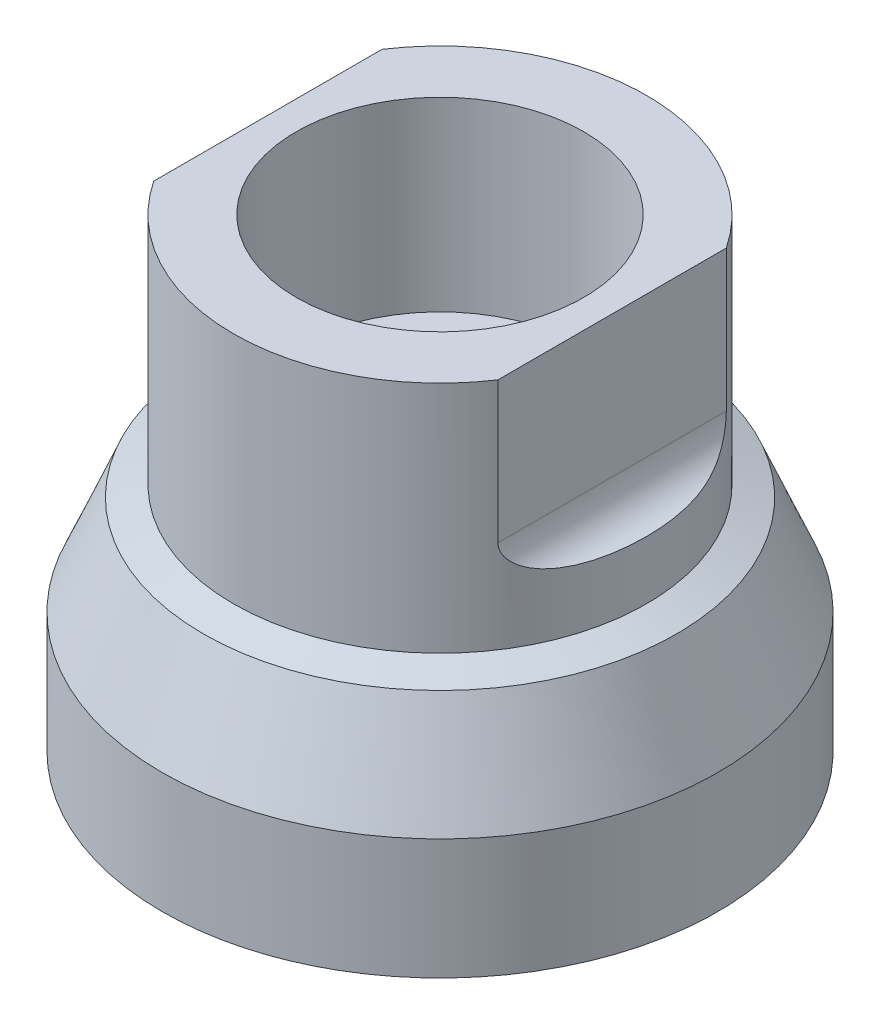
SolidWorks part; units mm, degrees
ref_plane "Front Plane" through (0, 0, 0) normal (0, 0, 1) x (1, 0, 0)
ref_plane "Top Plane" through (0, 0, 0) normal (0, 1, 0) x (1, 0, 0)
ref_plane "Right Plane" through (0, 0, 0) normal (1, 0, 0) x (0, 0, -1)
sketch "Sketch1" plane through (0, 0, 0) normal (1, 0, 0) x (0, 0, -1)
  line L0 (0, 0) -> (0, 17.2593) construction
  line L1 (0, 17.2593) -> (-15.24, 17.2593)
  line L2 (-15.24, 17.2593) -> (-15.24, 0)
  line L3 (-15.24, 0) -> (0, 0) construction
  line L4 (-15.24, 0) -> (-17.4625, -0.8089)
  line L5 (-17.4625, -0.8089) -> (-20.5105, -8.1407)
  line L6 (-20.5105, -17.0307) -> (-8.7845, -20.8407)
  line L7 (-8.7845, -20.8407) -> (0, -20.8407)
  line L8 (0, -20.8407) -> (0, 0) construction
  line L9 (-13.0457, 17.2593) -> (-13.0457, 0) construction
  line L10 (0, 17.2593) -> (0, -20.8407) construction
  line L11 (-20.5105, -8.1407) -> (-20.5105, -17.0307)
  line L12 (0, 17.2593) -> (0, -20.8407)
  dimension "D1" = 17.2593
  dimension "D2" = 38.1
  dimension "D3" = 110
  dimension "D4" = 41.021
  dimension "D5" = 38.1
  dimension "D6" = 30.48
  dimension "D7" = 25.4
  dimension "D8" = 34.29
  dimension "D9" = 18
  dimension "D10" = 34.925
revolve "Revolve1" add sketch "Sketch1" angle 360 mid plane about L12
sketch "Sketch3" plane through (0, 0, 0) normal (0, 0, 1) x (1, 0, 0)
  line L0 (-20.5105, -17.0307) -> (-8.7845, -20.8407) construction
  line L1 (-20.5105, -17.0307) -> (-5.161, -22.0181)
  line L2 (-12.8358, -19.5244) -> (-8.8848, -7.3647) construction
  point P7 (-8.7845, -20.8407)
  dimension "D1" = 3.81
ref_plane "Plane1" through (-5.872, 1.9079, 0) normal (0.9511, -0.309, 0) x (0, 0, -1)
sketch "Sketch4" plane through (-5.872, 1.9079, 0) normal (0.9511, -0.309, 0) x (0, 0, -1)
  line L0 (0, -25.0753) -> (0, -4.7553) construction
  line L1 (0, -7.7423) -> (0, -0.7693) construction
  line L2 (0, -4.7553) -> (-6.8326, -8.3882)
  line L3 (-6.8326, -8.3882) -> (-6.8326, -25.0753)
  line L4 (-6.8326, -25.0753) -> (0, -25.0753)
  line L5 (0, -25.0753) -> (0, -4.7553)
  dimension "D1" = 2.54
  dimension "D2" = 20.32
  dimension "D3" = 13.6652
  dimension "D4" = 118
revolve "Cut-Revolve2" cut sketch "Sketch4" angle 360 mid plane about L0
ref_plane "Plane2" through (-6.9638, -21.4323, 0) normal (-0.309, -0.9511, 0) x (0.9511, -0.309, 0)
ref_plane "Plane3" through (-7.3998, -22.7743, 0) normal (-0.309, -0.9511, 0) x (0.9511, -0.309, 0)
sketch "Sketch5" plane through (-7.3998, -22.7743, 0) normal (-0.309, -0.9511, 0) x (0.9511, -0.309, 0)
  circle A0 centre (-6.1742, 0) radius 6.858
  dimension "Outlet OD" = 13.716
curve "Helix/Spiral1"
sketch "Sketch8" plane through (0, 0, 0) normal (0, 0, 1) x (1, 0, 0)
  line L0 (0, -20.8407) -> (8.7845, -20.8407)
  line L1 (0, -17.0307) -> (0, -20.8407) construction
  line L2 (-7.6682, -20.8407) -> (8.7845, -20.8407) construction
  line L3 (8.7845, -20.8407) -> (20.5105, -17.0307) construction
  line L4 (8.7845, -20.8407) -> (20.5105, -17.0307)
  line L5 (20.5105, -17.0307) -> (20.5105, -33.1701)
  line L6 (20.5105, -33.1701) -> (0, -33.1701)
  line L7 (0, -33.1701) -> (0, -20.8407)
sketch "Sketch6" plane through (0, 0, 0) normal (0, 0, 1) x (1, 0, 0)
  line L0 (-12.8358, -19.5244) -> (-8.8848, -7.3647) construction
  line L4 (-6.2544, -21.7092) -> (-7.6347, -22.0025) construction
  line L5 (-7.6347, -22.0025) -> (-6.6904, -23.0512) construction
  line L6 (-6.6904, -23.0512) -> (-6.2544, -21.7092) construction
  line L7 (-7.4621, -21.9659) -> (-7.5166, -22.1336) construction
  line L8 (-6.4269, -21.7458) -> (-6.8085, -22.9201) construction
  line L9 (-7.6347, -22.0025) -> (-7.4894, -22.0497) construction
  line L10 (-6.6177, -22.333) -> (-6.4724, -22.3802) construction
  line L11 (-6.5451, -22.3566) -> (-6.7495, -22.9857) construction
  line L13 (-6.3407, -21.7275) -> (-7.4621, -21.9659)
  line L14 (-7.4621, -21.9659) -> (-7.5166, -22.1336)
  line L15 (-7.5166, -22.1336) -> (-6.6904, -23.0512)
  line L16 (-7.6347, -22.0025) -> (-8.6147, -21.6841) construction
  line L17 (-6.6904, -23.0512) -> (-6.5227, -23.1057) construction
  line L18 (-6.5227, -23.1057) -> (-6.4682, -22.938) construction
  line L19 (-6.4682, -22.938) -> (-6.4137, -22.7702) construction
  line L20 (-6.4137, -22.7702) -> (-6.3592, -22.6024) construction
  line L21 (-6.3592, -22.6024) -> (-6.3047, -22.4347) construction
  line L22 (-6.3047, -22.4347) -> (-6.2502, -22.2669) construction
  line L23 (-6.2502, -22.2669) -> (-6.1956, -22.0992) construction
  line L24 (-6.1956, -22.0992) -> (-6.1411, -21.9314) construction
  line L25 (-6.1411, -21.9314) -> (-6.0866, -21.7637) construction
  line L26 (-6.0866, -21.7637) -> (-6.2544, -21.7092) construction
  line L27 (-6.5451, -22.3566) -> (-6.3407, -21.7275) construction
  line L28 (-6.3407, -21.7275) -> (-6.6904, -23.0512)
  point P18 (-6.5099, -22.368)
  dimension "D1" = 1.4111
sweep "Sweep1" [suppressed] add profiles "Sketch6" path "Helix/Spiral1"
sketch "Sketch10" plane through (0, 0, 0) normal (0, 0, 1) x (1, 0, 0)
  line L0 (-12.8358, -19.5244) -> (-20.5105, -17.0307) construction
  line L1 (-20.5105, -17.0307) -> (-16.6639, -15.0708)
  line L2 (-16.6639, -15.0708) -> (-11.8924, -16.6211)
  line L3 (-12.8358, -19.5244) -> (-8.8848, -7.3647) construction
  line L4 (-11.8924, -16.6211) -> (-12.8358, -19.5244)
  line L6 (-20.5105, -17.0307) -> (-24.3571, -18.9906)
  line L7 (-24.3571, -18.9906) -> (-13.7791, -22.4276)
  line L8 (-13.7791, -22.4276) -> (-12.8358, -19.5244)
  point P4 (-18.5872, -16.0507)
  dimension "D1" = 45
  dimension "D2" = 3.8466
revolve "Cut-Revolve4" cut sketch "Sketch10" angle 360 mid plane about L8
pattern_circular "CirPattern1" count 3 over 360 about axis through (0, -0.8089, 0) along (0, 1, 0) of "Cut-Revolve2", "Sweep1", "Cut-Revolve4"
sketch "Sketch2" plane through (0, 0, 0) normal (0, 0, 1) x (1, 0, 0)
  line L0 (0, 17.2593) -> (0, -10.6807) construction
  line L1 (15.24, 17.2593) -> (-15.24, 17.2593) construction
  line L2 (0, -10.6807) -> (-7.8994, -6.4805)
  line L3 (-7.8994, -6.4805) -> (-7.8994, 17.2593)
  line L4 (-7.8994, 17.2593) -> (0, 17.2593)
  line L5 (0, 17.2593) -> (0, -10.6807)
  dimension "D1" = 118
  dimension "D2" = 27.94
  dimension "Schedule 40 ID" = 15.7988
revolve "Cut-Revolve1" cut sketch "Sketch2" angle 360 mid plane about L0
sketch "Sketch12" plane through (0, 17.2593, 0) normal (0, 1, 0) x (1, 0, 0)
  circle A0 centre (0, 0) radius 10.668
  dimension "D1" = 21.336
curve "Helix/Spiral2"
sketch "Sketch13" plane through (0, 17.2593, 0) normal (0, 1, 0) x (1, 0, 0)
  circle A0 centre (0, 0) radius 10.6045
  dimension "D1" = 21.209
extrude "Cut-Extrude1" cut sketch "Sketch13" against normal blind 13.716
sketch "Sketch19" plane through (0, 0, 0) normal (0, 0, 1) x (1, 0, 0)
  line L0 (-10.6045, 17.2593) -> (-10.6045, 3.5433) construction
  line L1 (10.6045, 3.5433) -> (10.6045, 17.2593) construction
  line L2 (-10.6045, 17.2593) -> (-10.6045, 3.5433)
  line L3 (10.6045, 3.5433) -> (10.6045, 17.2593)
  line L4 (10.6045, 3.5433) -> (-10.6045, 3.5433)
sketch "Sketch14" plane through (0, 0, 0) normal (1, 0, 0) x (0, 0, -1)
  line L0 (-10.7662, 17.2026) -> (-9.195, 18.1097) construction
  line L1 (-9.195, 18.1097) -> (-10.7662, 19.0169) construction
  line L2 (-10.7662, 19.0169) -> (-10.7662, 17.2026) construction
  line L3 (-9.3914, 17.9964) -> (-9.3914, 18.2231) construction
  line L4 (-10.5698, 17.316) -> (-10.5698, 18.9035) construction
  line L5 (-9.195, 18.1097) -> (-9.3914, 18.1097) construction
  line L6 (-10.5698, 18.1097) -> (-10.7662, 18.1097) construction
  line L7 (-10.668, 18.1097) -> (-10.668, 18.9602) construction
  line L8 (-10.668, 17.2593) -> (-9.3914, 17.9964)
  line L9 (-9.3914, 17.9964) -> (-9.3914, 18.2231)
  line L10 (-9.3914, 18.2231) -> (-10.7662, 19.0169)
  line L11 (-9.195, 18.1097) -> (-2.2184, 18.1097) construction
  line L12 (-10.7662, 19.0169) -> (-10.993, 19.0169) construction
  line L13 (-10.993, 19.0169) -> (-10.993, 18.7901) construction
  line L14 (-10.993, 18.7901) -> (-10.993, 18.5633) construction
  line L15 (-10.993, 18.5633) -> (-10.993, 18.3365) construction
  line L16 (-10.993, 18.3365) -> (-10.993, 18.1097) construction
  line L17 (-10.993, 18.1097) -> (-10.993, 17.883) construction
  line L18 (-10.993, 17.883) -> (-10.993, 17.6562) construction
  line L19 (-10.993, 17.6562) -> (-10.993, 17.4294) construction
  line L20 (-10.993, 17.4294) -> (-10.993, 17.2026) construction
  line L21 (-10.993, 17.2026) -> (-10.7662, 17.2026) construction
  line L22 (-10.668, 18.1097) -> (-10.668, 17.2593) construction
  line L23 (-10.668, 17.2593) -> (-10.7662, 19.0169)
  point P17 (-10.7155, 18.1097)
  dimension "Pitch Inlet" = 1.8143
sweep "Sweep2" [suppressed] add profiles "Sketch14" path "Helix/Spiral2"
sketch "Sketch15" plane through (0, 17.2593, 0) normal (0, 1, 0) x (1, 0, 0)
  circle A1 centre (0, 0) radius 15.24
  circle A2 centre (0, 0) radius 15.24
  dimension "D1" = 0
extrude "Cut-Extrude2" [suppressed] cut sketch "Sketch15" along normal blind 13.716
sketch "Sketch16" [suppressed] plane through (0, 17.2593, 0) normal (0, 1, 0) x (1, 0, 0)
  line L0 (2.0493, 10.3024) -> (0, 0) construction
  circle A0 centre (0, 0) radius 10.5042
  dimension "D1" = 1.143
extrude "Cut-Extrude3" [suppressed] cut sketch "Sketch16" against normal blind 13.716 draft 45
sketch "Sketch17" plane through (0, 0, 0) normal (0, 0, 1) x (1, 0, 0)
  line L0 (0, 0) -> (0, 17.2593) construction
  line L1 (-15.24, 17.2593) -> (-12.7, 17.2593)
  line L2 (-15.24, 17.2593) -> (-15.24, 4.3053)
  line L3 (-15.24, 4.3053) -> (-12.7, 4.3053)
  line L4 (-12.7, 17.2593) -> (-12.7, 4.3053)
  line L5 (15.24, 0) -> (-15.24, 0) construction
  line L6 (15.24, 17.2593) -> (-15.24, 17.2593) construction
  line L7 (12.7, 17.2593) -> (12.7, 4.3053)
  line L8 (15.24, 4.3053) -> (12.7, 4.3053)
  line L9 (15.24, 17.2593) -> (15.24, 4.3053)
  line L10 (15.24, 17.2593) -> (12.7, 17.2593)
  dimension "D1" = 25.4
  dimension "D2" = 12.954
extrude "Cut-Extrude4" cut sketch "Sketch17" against normal through all and the other way through all
fillet "Fillet1" radius 2.54 2 edges at (12.7, 4.3053, 0) (-12.7, 4.3053, 0)
sketch "Sketch20" plane through (0, 0, 0) normal (0, 1, 0) x (1, 0, 0)
  line L0 (-20.5105, 0) -> (20.5105, 0) construction
  line L1 (0, 20.5105) -> (0, -20.5105) construction
  circle A0 centre (0, 0) radius 20.5105 construction
  circle A1 centre (0, 0) radius 20.5105
sketch "Sketch21" [suppressed] plane through (0, -20.8407, 0) normal (0, -1, 0) x (1, 0, 0)
  line L0 (6.6317, 11.4865) -> (6.6317, -11.4865)
scale "Scale1" scale about centroid uniform scaling yes scale factor 1.5
